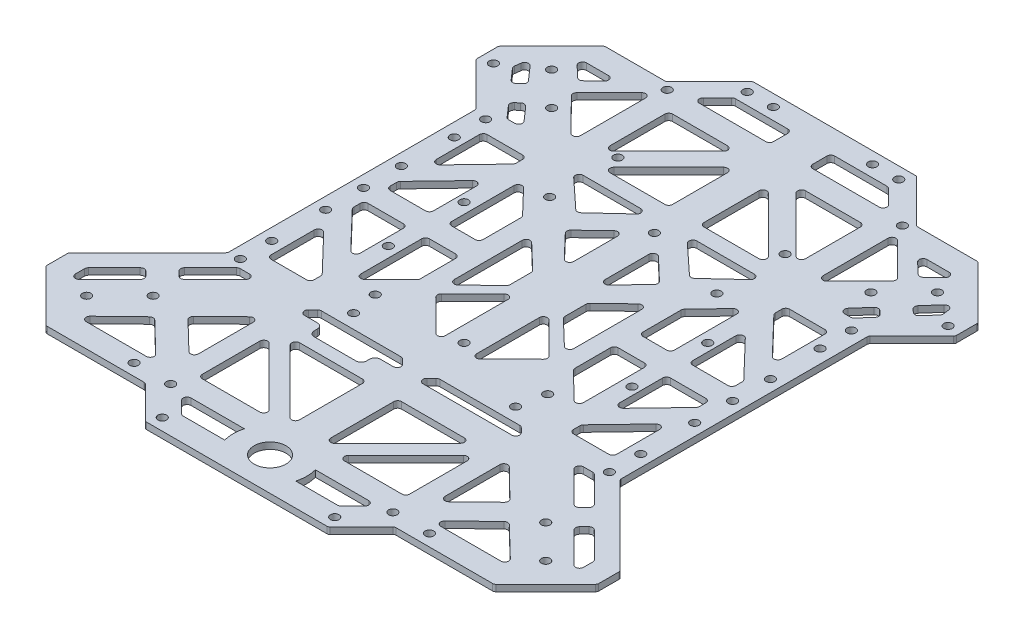
SolidWorks part; units mm, degrees
other "Kamera1"
ref_plane "Ön Düzlem" through (0, 0, 0) normal (0, 0, 1) x (1, 0, 0)
ref_plane "Üst Düzlem" through (0, 0, 0) normal (0, 1, 0) x (1, 0, 0)
ref_plane "Sağ Düzlem" through (0, 0, 0) normal (1, 0, 0) x (0, 0, -1)
sketch "Çizim1" plane through (0, 0, 0) normal (0, 1, 0) x (1, 0, 0)
  line L0 (-126.5115, 0) -> (-22.8808, 0) construction
  line L1 (0, -165.8604) -> (0, 125.495) construction
  line L10 (105.5269, -77.9056) -> (75.1213, -47.5)
  line L11 (105.5269, -86.6056) -> (105.5269, -77.9056)
  line L12 (85.7279, -106.4046) -> (105.5269, -86.6056)
  line L13 (47.7279, -106.4046) -> (85.7279, -106.4046)
  line L14 (35, -119.1325) -> (47.7279, -106.4046)
  line L15 (35, -119.1325) -> (-35, -119.1325)
  line L17 (75.1213, -47.5) -> (75.1213, 0)
  line L19 (6, -104.1325) -> (6, -108.6325)
  line L20 (7.5, -110.1325) -> (29.5, -110.1325)
  line L21 (30.5607, -109.6932) -> (35.0607, -105.1932)
  line L22 (34, -102.6325) -> (7.5, -102.6325)
  line L24 (39.6933, -70.6325) -> (39.6933, -92.6325)
  line L25 (38.1933, -94.1325) -> (16.1933, -94.1325)
  line L26 (15.1326, -91.5718) -> (37.1326, -69.5718)
  line L27 (6, -65.0493) -> (6, -89.1325)
  line L28 (8.5625, -90.1913) -> (32.5625, -66.1081)
  line L29 (31.5, -63.5493) -> (7.5, -63.5493)
  line L30 (66.8113, -83.7022) -> (55.3113, -94.8265)
  line L31 (56.3542, -97.4046) -> (79.3542, -97.4046)
  line L32 (80.3971, -94.8265) -> (68.8971, -83.7022)
  line L36 (49.7362, -87.6977) -> (60.5174, -77.2687)
  line L37 (60.5247, -75.1195) -> (49.7434, -64.5485)
  line L38 (47.1933, -65.6196) -> (47.1933, -86.6196)
  line L39 (21.6344, -34.0457) -> (4.6344, -50.9868)
  line L40 (5.6933, -53.5493) -> (39.6933, -53.5493)
  line L41 (40.7521, -50.9868) -> (23.7521, -34.0457)
  line L42 (6, -9.3078) -> (6, -33.3078)
  line L43 (8.5588, -34.3703) -> (20.6004, -22.3703)
  line L44 (20.6004, -20.2453) -> (8.5588, -8.2453)
  line L45 (10.5, 4) -> (10.5, -4)
  line L46 (10.9615, -5.0824) -> (20.3424, -14.0824)
  line L47 (22.8808, -13) -> (22.8808, 13)
  line L49 (84.7746, -69.1741) -> (83.0069, -70.9419)
  line L50 (83.0069, -73.0632) -> (94.6741, -84.7305)
  line L51 (97.2348, -83.6698) -> (97.2348, -80.1343)
  line L52 (96.7954, -79.0736) -> (86.8959, -69.1741)
  line L53 (87.603, -59.9817) -> (82.3234, -65.2614) construction
  line L54 (63.915, -50.35) -> (67.4505, -50.35)
  line L55 (74.5216, -64.5779) -> (62.8543, -52.9107)
  line L56 (78.4107, -62.8102) -> (76.6429, -64.5779)
  line L57 (68.5112, -50.7893) -> (78.4107, -60.6888)
  line L58 (51.1213, -41.35) -> (64.6213, -41.35)
  line L59 (66.1213, -39.85) -> (66.1213, -23.35)
  line L60 (63.5389, -22.3115) -> (50.0389, -36.3828)
  line L61 (49.6213, -37.4212) -> (49.6213, -39.85)
  line L62 (49.6213, -5.7546) -> (49.6213, -22.2546)
  line L63 (52.2037, -23.293) -> (65.7037, -9.2218)
  line L64 (66.1213, -8.1833) -> (66.1213, -5.7546)
  line L65 (64.6213, -4.2546) -> (51.1213, -4.2546)
  line L66 (29.6213, -5.75) -> (29.6213, -19.25)
  line L67 (30.0715, -20.3214) -> (40.0715, -30.1194)
  line L68 (42.6213, -29.048) -> (42.6213, -5.75)
  line L69 (41.1213, -4.25) -> (31.1213, -4.25)
  line L70 (-105.5269, -86.6056) -> (-105.5269, -77.9056)
  line L71 (-105.5269, -77.9056) -> (-75.1213, -47.5)
  line L72 (-85.7279, -106.4046) -> (-105.5269, -86.6056)
  line L73 (-87.603, -59.9817) -> (-82.3234, -65.2614) construction
  line L74 (-41.1213, -4.25) -> (-31.1213, -4.25)
  line L75 (-42.6213, -29.048) -> (-42.6213, -5.75)
  line L76 (-30.0715, -20.3214) -> (-40.0715, -30.1194)
  line L77 (-29.6213, -5.75) -> (-29.6213, -19.25)
  line L78 (-64.6213, -4.2546) -> (-51.1213, -4.2546)
  line L79 (-66.1213, -8.1833) -> (-66.1213, -5.7546)
  line L80 (-52.2037, -23.293) -> (-65.7037, -9.2218)
  line L81 (-49.6213, -5.7546) -> (-49.6213, -22.2546)
  line L82 (-49.6213, -37.4212) -> (-49.6213, -39.85)
  line L83 (-63.5389, -22.3115) -> (-50.0389, -36.3828)
  line L84 (-66.1213, -39.85) -> (-66.1213, -23.35)
  line L85 (-51.1213, -41.35) -> (-64.6213, -41.35)
  line L86 (-68.5112, -50.7893) -> (-78.4107, -60.6888)
  line L87 (-78.4107, -62.8102) -> (-76.6429, -64.5779)
  line L88 (-74.5216, -64.5779) -> (-62.8543, -52.9107)
  line L89 (-63.915, -50.35) -> (-67.4505, -50.35)
  line L90 (-96.7954, -79.0736) -> (-86.8959, -69.1741)
  line L91 (-97.2348, -83.6698) -> (-97.2348, -80.1343)
  line L92 (-83.0069, -73.0632) -> (-94.6741, -84.7305)
  line L93 (-84.7746, -69.1741) -> (-83.0069, -70.9419)
  line L95 (-22.8808, -13) -> (-22.8808, 0)
  line L96 (-10.9615, -5.0824) -> (-20.3424, -14.0824)
  line L97 (-10.5, 0) -> (-10.5, -4)
  line L98 (-20.6004, -20.2453) -> (-8.5588, -8.2453)
  line L99 (-8.5588, -34.3703) -> (-20.6004, -22.3703)
  line L100 (-6, -9.3078) -> (-6, -33.3078)
  line L101 (-40.7521, -50.9868) -> (-23.7521, -34.0457)
  line L102 (-5.6933, -53.5493) -> (-39.6933, -53.5493)
  line L103 (-21.6344, -34.0457) -> (-4.6344, -50.9868)
  line L104 (-47.1933, -65.6196) -> (-47.1933, -86.6196)
  line L105 (-60.5247, -75.1195) -> (-49.7434, -64.5485)
  line L106 (-49.7362, -87.6977) -> (-60.5174, -77.2687)
  line L107 (-80.3971, -94.8265) -> (-68.8971, -83.7022)
  line L108 (-56.3542, -97.4046) -> (-79.3542, -97.4046)
  line L109 (-66.8113, -83.7022) -> (-55.3113, -94.8265)
  line L110 (-31.5, -63.5493) -> (-7.5, -63.5493)
  line L111 (-8.5625, -90.1913) -> (-32.5625, -66.1081)
  line L112 (-6, -65.0493) -> (-6, -89.1325)
  line L113 (-15.1326, -91.5718) -> (-37.1326, -69.5718)
  line L114 (-38.1933, -94.1325) -> (-16.1933, -94.1325)
  line L115 (-39.6933, -70.6325) -> (-39.6933, -92.6325)
  line L116 (-34, -102.6325) -> (-7.5, -102.6325)
  line L117 (-30.5607, -109.6932) -> (-35.0607, -105.1932)
  line L118 (-7.5, -110.1325) -> (-29.5, -110.1325)
  line L119 (-6, -104.1325) -> (-6, -108.6325)
  line L120 (-75.1213, -47.5) -> (-75.1213, 0)
  line L121 (-35, -119.1325) -> (-47.7279, -106.4046)
  line L122 (-47.7279, -106.4046) -> (-85.7279, -106.4046)
  line L124 (75.1213, 0) -> (75.1213, 47.5)
  line L125 (75.1213, 47.5) -> (91.7383, 64.117)
  line L126 (91.7383, 64.117) -> (91.7383, 72.817)
  line L127 (91.7383, 72.817) -> (71.4444, 93.111)
  line L128 (71.4444, 93.111) -> (47.9444, 93.111)
  line L129 (47.9444, 93.111) -> (31.3274, 109.728)
  line L130 (31.3274, 109.728) -> (-31.3274, 109.728)
  line L131 (63.5389, 22.3115) -> (50.0389, 36.3828)
  line L132 (66.1213, 39.85) -> (66.1213, 23.35)
  line L133 (51.1213, 41.35) -> (64.6213, 41.35)
  line L134 (49.6213, 37.4212) -> (49.6213, 39.85)
  line L135 (66.1213, 8.1833) -> (66.1213, 5.7546)
  line L136 (52.2037, 23.293) -> (65.7037, 9.2218)
  line L137 (49.6213, 5.7546) -> (49.6213, 22.2546)
  line L138 (64.6213, 4.2546) -> (51.1213, 4.2546)
  line L139 (41.1213, 4.2546) -> (32.1213, 4.2546)
  line L140 (30.6213, 5.7546) -> (30.6213, 20.2546)
  line L141 (31.0389, 21.293) -> (40.0389, 30.6739)
  line L142 (42.6213, 29.6354) -> (42.6213, 5.7546)
  line L143 (10.9615, 5.0824) -> (20.3424, 14.0824)
  line L144 (22.8808, 0) -> (141.8188, 0) construction
  line L145 (62.0023, 52.8424) -> (66.6337, 58.0913)
  line L146 (68.7509, 58.2236) -> (70.0256, 57.0989)
  line L147 (70.1579, 54.9817) -> (66.519, 50.8576)
  line L150 (65.3942, 50.35) -> (63.1271, 50.35)
  line L151 (70.1198, 63.017) -> (74.1298, 59.4788) construction
  line L152 (78.0974, 63.9797) -> (81.7363, 68.1038)
  line L153 (74.7055, 64.9722) -> (75.9802, 63.8474)
  line L154 (79.2045, 72.3382) -> (74.5731, 67.0894)
  line L155 (82.0999, 69.283) -> (81.8176, 71.5326)
  line L156 (60.9579, 84.111) -> (69.3579, 84.111)
  line L157 (70.3923, 81.5248) -> (66.1923, 77.5248)
  line L158 (64.1234, 77.5248) -> (59.9234, 81.5248)
  line L159 (6, 32.6354) -> (6, 15.8354)
  line L160 (8.585, 14.7997) -> (16.976, 23.5902)
  line L161 (16.9266, 25.7109) -> (8.5357, 33.7204)
  line L162 (9.7302, 43.598) -> (20.7302, 33.4)
  line L163 (22.7698, 33.4) -> (33.7698, 43.598)
  line L164 (32.75, 46.198) -> (10.75, 46.198)
  line L165 (9, 100.728) -> (29.0094, 100.728)
  line L166 (30.071, 100.2877) -> (35.4616, 94.8877)
  line L167 (34.4, 92.328) -> (9, 92.328)
  line L168 (7.5, 93.828) -> (7.5, 99.228)
  line L169 (6, 74.698) -> (6, 53.698)
  line L170 (7.5, 52.198) -> (28.5, 52.198)
  line L171 (29.5607, 54.7587) -> (8.5607, 75.7587)
  line L172 (16.4335, 73.1892) -> (24.0883, 65.5343) construction
  line L173 (37.4246, 82.1227) -> (37.4246, 61.1227)
  line L174 (14.9246, 83.6227) -> (35.9246, 83.6227)
  line L175 (34.864, 60.062) -> (13.864, 81.062)
  line L176 (46.4246, 83.7244) -> (46.4246, 58.8244)
  line L177 (48.9917, 57.7702) -> (61.3661, 70.2958)
  line L178 (61.3597, 72.4107) -> (48.9853, 84.785)
  line L179 (-10.5, 0) -> (10.5, 0) construction
  line L180 (-22.8808, -13) -> (-22.8808, 13)
  line L181 (-10.5, 4) -> (-10.5, -4)
  line L182 (-75.1213, 0) -> (-75.1213, 47.5)
  line L183 (-16.4335, 73.1892) -> (-24.0883, 65.5343) construction
  line L184 (-61.3597, 72.4107) -> (-48.9853, 84.785)
  line L185 (-48.9917, 57.7702) -> (-61.3661, 70.2958)
  line L186 (-46.4246, 83.7244) -> (-46.4246, 58.8244)
  line L187 (-34.864, 60.062) -> (-13.864, 81.062)
  line L188 (-14.9246, 83.6227) -> (-35.9246, 83.6227)
  line L189 (-37.4246, 82.1227) -> (-37.4246, 61.1227)
  line L190 (-29.5607, 54.7587) -> (-8.5607, 75.7587)
  line L191 (-7.5, 52.198) -> (-28.5, 52.198)
  line L192 (-6, 74.698) -> (-6, 53.698)
  line L193 (-7.5, 93.828) -> (-7.5, 99.228)
  line L194 (-34.4, 92.328) -> (-9, 92.328)
  line L195 (-30.071, 100.2877) -> (-35.4616, 94.8877)
  line L196 (-9, 100.728) -> (-29.0094, 100.728)
  line L197 (-32.75, 46.198) -> (-10.75, 46.198)
  line L198 (-22.7698, 33.4) -> (-33.7698, 43.598)
  line L199 (-9.7302, 43.598) -> (-20.7302, 33.4)
  line L200 (-16.9266, 25.7109) -> (-8.5357, 33.7204)
  line L201 (-8.585, 14.7997) -> (-16.976, 23.5902)
  line L202 (-6, 32.6354) -> (-6, 15.8354)
  line L203 (-64.1234, 77.5248) -> (-59.9234, 81.5248)
  line L204 (-70.3923, 81.5248) -> (-66.1923, 77.5248)
  line L205 (-60.9579, 84.111) -> (-69.3579, 84.111)
  line L206 (-82.0999, 69.283) -> (-81.8176, 71.5326)
  line L207 (-79.2045, 72.3382) -> (-74.5731, 67.0894)
  line L208 (-74.7055, 64.9722) -> (-75.9802, 63.8474)
  line L209 (-78.0974, 63.9797) -> (-81.7363, 68.1038)
  line L210 (-10.9615, 5.0824) -> (-20.3424, 14.0824)
  line L211 (-42.6213, 29.6354) -> (-42.6213, 5.7546)
  line L212 (-31.0389, 21.293) -> (-40.0389, 30.6739)
  line L213 (-30.6213, 5.7546) -> (-30.6213, 20.2546)
  line L214 (-41.1213, 4.2546) -> (-32.1213, 4.2546)
  line L215 (-64.6213, 4.2546) -> (-51.1213, 4.2546)
  line L216 (-49.6213, 5.7546) -> (-49.6213, 22.2546)
  line L217 (-52.2037, 23.293) -> (-65.7037, 9.2218)
  line L218 (-66.1213, 8.1833) -> (-66.1213, 5.7546)
  line L219 (-49.6213, 37.4212) -> (-49.6213, 39.85)
  line L220 (-51.1213, 41.35) -> (-64.6213, 41.35)
  line L221 (-66.1213, 39.85) -> (-66.1213, 23.35)
  line L222 (-63.5389, 22.3115) -> (-50.0389, 36.3828)
  line L223 (-47.9444, 93.111) -> (-31.3274, 109.728)
  line L224 (-71.4444, 93.111) -> (-47.9444, 93.111)
  line L225 (-91.7383, 72.817) -> (-71.4444, 93.111)
  line L226 (-91.7383, 64.117) -> (-91.7383, 72.817)
  line L227 (-75.1213, 47.5) -> (-91.7383, 64.117)
  line L228 (-70.1579, 54.9817) -> (-66.519, 50.8576)
  line L229 (-68.7509, 58.2236) -> (-70.0256, 57.0989)
  line L230 (-62.0023, 52.8424) -> (-66.6337, 58.0913)
  line L231 (-65.3942, 50.35) -> (-63.1271, 50.35)
  arc A0 (29.5, -110.1325) -> (30.5607, -109.6932) centre (29.5, -108.6325) ccw
  arc A1 (35.0607, -105.1932) -> (34, -102.6325) centre (34, -104.1325) ccw
  arc A2 (6, -104.1325) -> (7.5, -102.6325) centre (7.5, -104.1325) cw
  arc A3 (6, -108.6325) -> (7.5, -110.1325) centre (7.5, -108.6325) ccw
  arc A4 (39.6933, -70.6325) -> (37.1326, -69.5718) centre (38.1933, -70.6325) ccw
  arc A5 (39.6933, -92.6325) -> (38.1933, -94.1325) centre (38.1933, -92.6325) cw
  arc A6 (16.1933, -94.1325) -> (15.1326, -91.5718) centre (16.1933, -92.6325) cw
  arc A7 (6, -89.1325) -> (8.5625, -90.1913) centre (7.5, -89.1325) ccw
  arc A8 (32.5625, -66.1081) -> (31.5, -63.5493) centre (31.5, -65.0493) ccw
  arc A9 (6, -65.0493) -> (7.5, -63.5493) centre (7.5, -65.0493) cw
  arc A10 (79.3542, -97.4046) -> (80.3971, -94.8265) centre (79.3542, -95.9046) ccw
  arc A11 (55.3113, -94.8265) -> (56.3542, -97.4046) centre (56.3542, -95.9046) ccw
  arc A12 (66.8113, -83.7022) -> (68.8971, -83.7022) centre (67.8542, -84.7803) cw
  arc A16 (60.5174, -77.2687) -> (60.5247, -75.1195) centre (59.4745, -76.1905) ccw
  arc A17 (49.7434, -64.5485) -> (47.1933, -65.6196) centre (48.6933, -65.6196) ccw
  arc A18 (49.7362, -87.6977) -> (47.1933, -86.6196) centre (48.6933, -86.6196) cw
  arc A19 (39.6933, -53.5493) -> (40.7521, -50.9868) centre (39.6933, -52.0493) ccw
  arc A20 (4.6344, -50.9868) -> (5.6933, -53.5493) centre (5.6933, -52.0493) ccw
  arc A21 (21.6344, -34.0457) -> (23.7521, -34.0457) centre (22.6933, -35.1082) cw
  arc A22 (6, -9.3078) -> (8.5588, -8.2453) centre (7.5, -9.3078) cw
  arc A23 (20.6004, -22.3703) -> (20.6004, -20.2453) centre (19.5416, -21.3078) ccw
  arc A24 (6, -33.3078) -> (8.5588, -34.3703) centre (7.5, -33.3078) ccw
  arc A25 (20.3424, -14.0824) -> (22.8808, -13) centre (21.3808, -13) ccw
  arc A26 (10.5, -4) -> (10.9615, -5.0824) centre (12, -4) ccw
  arc A27 (83.0069, -70.9419) -> (83.0069, -73.0632) centre (84.0675, -72.0025) ccw
  arc A28 (84.7746, -69.1741) -> (86.8959, -69.1741) centre (85.8353, -70.2348) cw
  arc A29 (97.2348, -80.1343) -> (96.7954, -79.0736) centre (95.7348, -80.1343) ccw
  arc A30 (94.6741, -84.7305) -> (97.2348, -83.6698) centre (95.7348, -83.6698) ccw
  arc A31 (62.8543, -52.9107) -> (63.915, -50.35) centre (63.915, -51.85) cw
  arc A32 (76.6429, -64.5779) -> (74.5216, -64.5779) centre (75.5822, -63.5173) cw
  arc A33 (78.4107, -62.8102) -> (78.4107, -60.6888) centre (77.35, -61.7495) ccw
  arc A34 (67.4505, -50.35) -> (68.5112, -50.7893) centre (67.4505, -51.85) cw
  arc A35 (66.1213, -23.35) -> (63.5389, -22.3115) centre (64.6213, -23.35) ccw
  arc A36 (64.6213, -41.35) -> (66.1213, -39.85) centre (64.6213, -39.85) ccw
  arc A37 (51.1213, -41.35) -> (49.6213, -39.85) centre (51.1213, -39.85) cw
  arc A38 (50.0389, -36.3828) -> (49.6213, -37.4212) centre (51.1213, -37.4212) ccw
  arc A39 (66.1213, -5.7546) -> (64.6213, -4.2546) centre (64.6213, -5.7546) ccw
  arc A40 (65.7037, -9.2218) -> (66.1213, -8.1833) centre (64.6213, -8.1833) ccw
  arc A41 (49.6213, -22.2546) -> (52.2037, -23.293) centre (51.1213, -22.2546) ccw
  arc A42 (49.6213, -5.7546) -> (51.1213, -4.2546) centre (51.1213, -5.7546) cw
  arc A43 (29.6213, -5.75) -> (31.1213, -4.25) centre (31.1213, -5.75) cw
  arc A44 (42.6213, -5.75) -> (41.1213, -4.25) centre (41.1213, -5.75) ccw
  arc A45 (40.0715, -30.1194) -> (42.6213, -29.048) centre (41.1213, -29.048) ccw
  arc A46 (29.6213, -19.25) -> (30.0715, -20.3214) centre (31.1213, -19.25) ccw
  arc A47 (-29.6213, -19.25) -> (-30.0715, -20.3214) centre (-31.1213, -19.25) cw
  arc A48 (-40.0715, -30.1194) -> (-42.6213, -29.048) centre (-41.1213, -29.048) cw
  arc A49 (-42.6213, -5.75) -> (-41.1213, -4.25) centre (-41.1213, -5.75) cw
  arc A50 (-29.6213, -5.75) -> (-31.1213, -4.25) centre (-31.1213, -5.75) ccw
  arc A51 (-49.6213, -5.7546) -> (-51.1213, -4.2546) centre (-51.1213, -5.7546) ccw
  arc A52 (-49.6213, -22.2546) -> (-52.2037, -23.293) centre (-51.1213, -22.2546) cw
  arc A53 (-65.7037, -9.2218) -> (-66.1213, -8.1833) centre (-64.6213, -8.1833) cw
  arc A54 (-66.1213, -5.7546) -> (-64.6213, -4.2546) centre (-64.6213, -5.7546) cw
  arc A55 (-50.0389, -36.3828) -> (-49.6213, -37.4212) centre (-51.1213, -37.4212) cw
  arc A56 (-51.1213, -41.35) -> (-49.6213, -39.85) centre (-51.1213, -39.85) ccw
  arc A57 (-64.6213, -41.35) -> (-66.1213, -39.85) centre (-64.6213, -39.85) cw
  arc A58 (-66.1213, -23.35) -> (-63.5389, -22.3115) centre (-64.6213, -23.35) cw
  arc A59 (-67.4505, -50.35) -> (-68.5112, -50.7893) centre (-67.4505, -51.85) ccw
  arc A60 (-78.4107, -62.8102) -> (-78.4107, -60.6888) centre (-77.35, -61.7495) cw
  arc A61 (-76.6429, -64.5779) -> (-74.5216, -64.5779) centre (-75.5822, -63.5173) ccw
  arc A62 (-62.8543, -52.9107) -> (-63.915, -50.35) centre (-63.915, -51.85) ccw
  arc A63 (-94.6741, -84.7305) -> (-97.2348, -83.6698) centre (-95.7348, -83.6698) cw
  arc A64 (-97.2348, -80.1343) -> (-96.7954, -79.0736) centre (-95.7348, -80.1343) cw
  arc A65 (-84.7746, -69.1741) -> (-86.8959, -69.1741) centre (-85.8353, -70.2348) ccw
  arc A66 (-83.0069, -70.9419) -> (-83.0069, -73.0632) centre (-84.0675, -72.0025) cw
  arc A67 (-10.5, -4) -> (-10.9615, -5.0824) centre (-12, -4) cw
  arc A68 (-20.3424, -14.0824) -> (-22.8808, -13) centre (-21.3808, -13) cw
  arc A69 (-6, -33.3078) -> (-8.5588, -34.3703) centre (-7.5, -33.3078) cw
  arc A70 (-20.6004, -22.3703) -> (-20.6004, -20.2453) centre (-19.5416, -21.3078) cw
  arc A71 (-6, -9.3078) -> (-8.5588, -8.2453) centre (-7.5, -9.3078) ccw
  arc A72 (-21.6344, -34.0457) -> (-23.7521, -34.0457) centre (-22.6933, -35.1082) ccw
  arc A73 (-4.6344, -50.9868) -> (-5.6933, -53.5493) centre (-5.6933, -52.0493) cw
  arc A74 (-39.6933, -53.5493) -> (-40.7521, -50.9868) centre (-39.6933, -52.0493) cw
  arc A75 (-49.7362, -87.6977) -> (-47.1933, -86.6196) centre (-48.6933, -86.6196) ccw
  arc A76 (-49.7434, -64.5485) -> (-47.1933, -65.6196) centre (-48.6933, -65.6196) cw
  arc A77 (-60.5174, -77.2687) -> (-60.5247, -75.1195) centre (-59.4745, -76.1905) cw
  arc A78 (-66.8113, -83.7022) -> (-68.8971, -83.7022) centre (-67.8542, -84.7803) ccw
  arc A79 (-55.3113, -94.8265) -> (-56.3542, -97.4046) centre (-56.3542, -95.9046) cw
  arc A80 (-79.3542, -97.4046) -> (-80.3971, -94.8265) centre (-79.3542, -95.9046) cw
  arc A81 (-6, -65.0493) -> (-7.5, -63.5493) centre (-7.5, -65.0493) ccw
  arc A82 (-32.5625, -66.1081) -> (-31.5, -63.5493) centre (-31.5, -65.0493) cw
  arc A83 (-6, -89.1325) -> (-8.5625, -90.1913) centre (-7.5, -89.1325) cw
  arc A84 (-16.1933, -94.1325) -> (-15.1326, -91.5718) centre (-16.1933, -92.6325) ccw
  arc A85 (-39.6933, -92.6325) -> (-38.1933, -94.1325) centre (-38.1933, -92.6325) ccw
  arc A86 (-39.6933, -70.6325) -> (-37.1326, -69.5718) centre (-38.1933, -70.6325) cw
  arc A87 (-6, -108.6325) -> (-7.5, -110.1325) centre (-7.5, -108.6325) cw
  arc A88 (-6, -104.1325) -> (-7.5, -102.6325) centre (-7.5, -104.1325) ccw
  arc A89 (-35.0607, -105.1932) -> (-34, -102.6325) centre (-34, -104.1325) cw
  arc A90 (-29.5, -110.1325) -> (-30.5607, -109.6932) centre (-29.5, -108.6325) cw
  arc A91 (66.1213, 23.35) -> (63.5389, 22.3115) centre (64.6213, 23.35) cw
  arc A92 (64.6213, 41.35) -> (66.1213, 39.85) centre (64.6213, 39.85) cw
  arc A93 (51.1213, 41.35) -> (49.6213, 39.85) centre (51.1213, 39.85) ccw
  arc A94 (50.0389, 36.3828) -> (49.6213, 37.4212) centre (51.1213, 37.4212) cw
  arc A95 (65.7037, 9.2218) -> (66.1213, 8.1833) centre (64.6213, 8.1833) cw
  arc A96 (49.6213, 22.2546) -> (52.2037, 23.293) centre (51.1213, 22.2546) cw
  arc A97 (66.1213, 5.7546) -> (64.6213, 4.2546) centre (64.6213, 5.7546) cw
  arc A98 (49.6213, 5.7546) -> (51.1213, 4.2546) centre (51.1213, 5.7546) ccw
  arc A99 (32.1213, 4.2546) -> (30.6213, 5.7546) centre (32.1213, 5.7546) cw
  arc A100 (41.1213, 4.2546) -> (42.6213, 5.7546) centre (41.1213, 5.7546) ccw
  arc A101 (40.0389, 30.6739) -> (42.6213, 29.6354) centre (41.1213, 29.6354) cw
  arc A102 (30.6213, 20.2546) -> (31.0389, 21.293) centre (32.1213, 20.2546) cw
  arc A103 (10.5, 4) -> (10.9615, 5.0824) centre (12, 4) cw
  arc A104 (20.3424, 14.0824) -> (22.8808, 13) centre (21.3808, 13) cw
  arc A105 (66.6337, 58.0913) -> (68.7509, 58.2236) centre (67.7584, 57.0989) cw
  arc A106 (70.0256, 57.0989) -> (70.1579, 54.9817) centre (69.0332, 55.9741) cw
  arc A107 (66.519, 50.8576) -> (65.3942, 50.35) centre (65.3942, 51.85) cw
  arc A108 (62.0023, 52.8424) -> (63.1271, 50.35) centre (63.1271, 51.85) ccw
  arc A109 (75.9802, 63.8474) -> (78.0974, 63.9797) centre (76.9726, 64.9722) ccw
  arc A110 (74.5731, 67.0894) -> (74.7055, 64.9722) centre (75.6979, 66.0969) ccw
  arc A111 (81.7363, 68.1038) -> (82.0999, 69.283) centre (80.6115, 69.0963) ccw
  arc A112 (79.2045, 72.3382) -> (81.8176, 71.5326) centre (80.3292, 71.3458) cw
  arc A113 (69.3579, 84.111) -> (70.3923, 81.5248) centre (69.3579, 82.611) cw
  arc A114 (66.1923, 77.5248) -> (64.1234, 77.5248) centre (65.1579, 78.611) cw
  arc A115 (60.9579, 84.111) -> (59.9234, 81.5248) centre (60.9579, 82.611) ccw
  arc A116 (16.976, 23.5902) -> (16.9266, 25.7109) centre (15.8909, 24.6259) ccw
  arc A117 (6, 15.8354) -> (8.585, 14.7997) centre (7.5, 15.8354) ccw
  arc A118 (6, 32.6354) -> (8.5357, 33.7204) centre (7.5, 32.6354) cw
  arc A119 (33.7698, 43.598) -> (32.75, 46.198) centre (32.75, 44.698) ccw
  arc A120 (20.7302, 33.4) -> (22.7698, 33.4) centre (21.75, 34.5) ccw
  arc A121 (9.7302, 43.598) -> (10.75, 46.198) centre (10.75, 44.698) cw
  arc A122 (35.4616, 94.8877) -> (34.4, 92.328) centre (34.4, 93.828) cw
  arc A123 (29.0094, 100.728) -> (30.071, 100.2877) centre (29.0094, 99.228) cw
  arc A124 (9, 100.728) -> (7.5, 99.228) centre (9, 99.228) ccw
  arc A125 (9, 92.328) -> (7.5, 93.828) centre (9, 93.828) cw
  arc A126 (28.5, 52.198) -> (29.5607, 54.7587) centre (28.5, 53.698) ccw
  arc A127 (6, 53.698) -> (7.5, 52.198) centre (7.5, 53.698) ccw
  arc A128 (6, 74.698) -> (8.5607, 75.7587) centre (7.5, 74.698) cw
  arc A129 (35.9246, 83.6227) -> (37.4246, 82.1227) centre (35.9246, 82.1227) cw
  arc A130 (37.4246, 61.1227) -> (34.864, 60.062) centre (35.9246, 61.1227) cw
  arc A131 (14.9246, 83.6227) -> (13.864, 81.062) centre (14.9246, 82.1227) ccw
  arc A132 (46.4246, 83.7244) -> (48.9853, 84.785) centre (47.9246, 83.7244) cw
  arc A133 (46.4246, 58.8244) -> (48.9917, 57.7702) centre (47.9246, 58.8244) ccw
  arc A134 (61.3661, 70.2958) -> (61.3597, 72.4107) centre (60.299, 71.35) ccw
  arc A135 (-61.3661, 70.2958) -> (-61.3597, 72.4107) centre (-60.299, 71.35) cw
  arc A136 (-46.4246, 58.8244) -> (-48.9917, 57.7702) centre (-47.9246, 58.8244) cw
  arc A137 (-46.4246, 83.7244) -> (-48.9853, 84.785) centre (-47.9246, 83.7244) ccw
  arc A138 (-14.9246, 83.6227) -> (-13.864, 81.062) centre (-14.9246, 82.1227) cw
  arc A139 (-37.4246, 61.1227) -> (-34.864, 60.062) centre (-35.9246, 61.1227) ccw
  arc A140 (-35.9246, 83.6227) -> (-37.4246, 82.1227) centre (-35.9246, 82.1227) ccw
  arc A141 (-6, 74.698) -> (-8.5607, 75.7587) centre (-7.5, 74.698) ccw
  arc A142 (-6, 53.698) -> (-7.5, 52.198) centre (-7.5, 53.698) cw
  arc A143 (-28.5, 52.198) -> (-29.5607, 54.7587) centre (-28.5, 53.698) cw
  arc A144 (-9, 92.328) -> (-7.5, 93.828) centre (-9, 93.828) ccw
  arc A145 (-9, 100.728) -> (-7.5, 99.228) centre (-9, 99.228) cw
  arc A146 (-29.0094, 100.728) -> (-30.071, 100.2877) centre (-29.0094, 99.228) ccw
  arc A147 (-35.4616, 94.8877) -> (-34.4, 92.328) centre (-34.4, 93.828) ccw
  arc A148 (-9.7302, 43.598) -> (-10.75, 46.198) centre (-10.75, 44.698) ccw
  arc A149 (-20.7302, 33.4) -> (-22.7698, 33.4) centre (-21.75, 34.5) cw
  arc A150 (-33.7698, 43.598) -> (-32.75, 46.198) centre (-32.75, 44.698) cw
  arc A151 (-6, 32.6354) -> (-8.5357, 33.7204) centre (-7.5, 32.6354) ccw
  arc A152 (-6, 15.8354) -> (-8.585, 14.7997) centre (-7.5, 15.8354) cw
  arc A153 (-16.976, 23.5902) -> (-16.9266, 25.7109) centre (-15.8909, 24.6259) cw
  arc A154 (-60.9579, 84.111) -> (-59.9234, 81.5248) centre (-60.9579, 82.611) cw
  arc A155 (-66.1923, 77.5248) -> (-64.1234, 77.5248) centre (-65.1579, 78.611) ccw
  arc A156 (-69.3579, 84.111) -> (-70.3923, 81.5248) centre (-69.3579, 82.611) ccw
  arc A157 (-79.2045, 72.3382) -> (-81.8176, 71.5326) centre (-80.3292, 71.3458) ccw
  arc A158 (-81.7363, 68.1038) -> (-82.0999, 69.283) centre (-80.6115, 69.0963) cw
  arc A159 (-74.5731, 67.0894) -> (-74.7055, 64.9722) centre (-75.6979, 66.0969) cw
  arc A160 (-75.9802, 63.8474) -> (-78.0974, 63.9797) centre (-76.9726, 64.9722) cw
  arc A161 (-20.3424, 14.0824) -> (-22.8808, 13) centre (-21.3808, 13) ccw
  arc A162 (-10.5, 4) -> (-10.9615, 5.0824) centre (-12, 4) ccw
  arc A163 (-30.6213, 20.2546) -> (-31.0389, 21.293) centre (-32.1213, 20.2546) ccw
  arc A164 (-40.0389, 30.6739) -> (-42.6213, 29.6354) centre (-41.1213, 29.6354) ccw
  arc A165 (-41.1213, 4.2546) -> (-42.6213, 5.7546) centre (-41.1213, 5.7546) cw
  arc A166 (-32.1213, 4.2546) -> (-30.6213, 5.7546) centre (-32.1213, 5.7546) ccw
  arc A167 (-49.6213, 5.7546) -> (-51.1213, 4.2546) centre (-51.1213, 5.7546) cw
  arc A168 (-66.1213, 5.7546) -> (-64.6213, 4.2546) centre (-64.6213, 5.7546) ccw
  arc A169 (-49.6213, 22.2546) -> (-52.2037, 23.293) centre (-51.1213, 22.2546) ccw
  arc A170 (-65.7037, 9.2218) -> (-66.1213, 8.1833) centre (-64.6213, 8.1833) ccw
  arc A171 (-50.0389, 36.3828) -> (-49.6213, 37.4212) centre (-51.1213, 37.4212) ccw
  arc A172 (-51.1213, 41.35) -> (-49.6213, 39.85) centre (-51.1213, 39.85) cw
  arc A173 (-64.6213, 41.35) -> (-66.1213, 39.85) centre (-64.6213, 39.85) ccw
  arc A174 (-66.1213, 23.35) -> (-63.5389, 22.3115) centre (-64.6213, 23.35) ccw
  arc A175 (-70.0256, 57.0989) -> (-70.1579, 54.9817) centre (-69.0332, 55.9741) ccw
  arc A176 (-66.6337, 58.0913) -> (-68.7509, 58.2236) centre (-67.7584, 57.0989) ccw
  arc A177 (-66.519, 50.8576) -> (-65.3942, 50.35) centre (-65.3942, 51.85) ccw
  arc A178 (-62.0023, 52.8424) -> (-63.1271, 50.35) centre (-63.1271, 51.85) cw
  point P14 (75.1213, 0)
  point P24 (0, -119.1325)
  point P29 (-95, 0)
  point P33 (0, 119.1325)
  point P105 (83.8907, -70.058)
  point P152 (42.6213, -32.6177)
  point P155 (29.6213, -19.8803)
  point P298 (0, -119.1325)
  point P299 (-29.6213, -19.8803)
  point P300 (-42.6213, -32.6177)
  point P301 (-75.1213, 0)
  point P357 (67.6261, 59.2161)
  point P360 (71.1503, 56.1064)
  point P363 (66.0711, 50.35)
  point P366 (59.8031, 50.35)
  point P367 (69.3882, 57.6612)
  point P368 (64.2607, 50.35)
  point P577 (0, 109.728)
  dimension "D18" = 1.5
  dimension "D15" = 28
  dimension "D19" = 1.5
  dimension "D24" = 1.5
  dimension "D29" = 1.5
  dimension "D35" = 1.5
  dimension "D39" = 1.5
  dimension "D28" = 1.5
  dimension "D51" = 1.5
  dimension "D55" = 1.5
  dimension "D62" = 1.5
  dimension "D68" = 1.5
  dimension "D75" = 1.5
  dimension "D89" = 1.5
  dimension "D97" = 1.5
  dimension "D102" = 1.5
  dimension "D106" = 1.5
  dimension "D111" = 1.5
  dimension "D112" = 15
  dimension "D113" = 15
  dimension "D115" = 10.75
  dimension "D117" = 1.5
  dimension "D118" = 1.5
  dimension "D119" = 1.5
  dimension "D120" = 1.5
  dimension "D126" = 1.5
  dimension "D127" = 1.5
  dimension "D128" = 1.5
  dimension "D134" = 1.5
  dimension "D135" = 1.5
  dimension "D136" = 1.5
  dimension "D1" = 47.5
  dimension "D2" = 18
  dimension "D3" = 43
  dimension "D4" = 8.7
  dimension "D5" = 28
  dimension "D6" = 38
  dimension "D7" = 35
  dimension "D8" = 135
  dimension "D9" = 225
  dimension "D10" = 135
  dimension "D11" = 135
  dimension "D12" = 135
  dimension "D13" = 7.5
  dimension "D14" = 9
  dimension "D16" = 6
  dimension "D17" = 135
  dimension "D20" = 22
  dimension "D21" = 7.5
  dimension "D22" = 25
  dimension "D23" = 22
  dimension "D25" = 24
  dimension "D26" = 15
  dimension "D27" = 34
  dimension "D30" = 16
  dimension "D31" = 16
  dimension "D32" = 23
  dimension "D33" = 9
  dimension "D34" = 30
  dimension "D36" = 21
  dimension "D37" = 15
  dimension "D38" = 9
  dimension "D40" = 30
  dimension "D41" = 10
  dimension "D42" = 24
  dimension "D43" = 24
  dimension "D44" = 34
  dimension "D45" = 6
  dimension "D46" = 24
  dimension "D47" = 17
  dimension "D48" = 17
  dimension "D49" = 9
  dimension "D50" = 13
  dimension "D52" = 13
  dimension "D53" = 10.5
  dimension "D54" = 4
  dimension "D56" = 7
  dimension "D57" = 5.5
  dimension "D58" = 16.5
  dimension "D59" = 14
  dimension "D60" = 9
  dimension "D61" = 4.5
  dimension "D63" = 13.5
  dimension "D64" = 19.5
  dimension "D65" = 16.5
  dimension "D66" = 9
  dimension "D67" = 9
  dimension "D69" = 19.5
  dimension "D70" = 16.5
  dimension "D71" = 13.5
  dimension "D72" = 9
  dimension "D73" = 7.5
  dimension "D74" = 14
  dimension "D76" = 13.5
  dimension "D77" = 10
  dimension "D78" = 7
  dimension "D79" = 4.25
  dimension "D80" = 47.5
  dimension "D81" = 23.5
  dimension "D82" = 8.7
  dimension "D83" = 28.7
  dimension "D84" = 23.5
  dimension "D85" = 23.5
  dimension "D86" = 135
  dimension "D87" = 135
  dimension "D88" = 7
  dimension "D90" = 12
  dimension "D91" = 13
  dimension "D92" = 14.5
  dimension "D93" = 135
  dimension "D94" = 135
  dimension "D95" = 7
  dimension "D96" = 5.5
  dimension "D98" = 4.7
  dimension "D99" = 9
  dimension "D100" = 8.8
  dimension "D101" = 4.5
  dimension "D103" = 5.8
  dimension "D104" = 9
  dimension "D105" = 8.9
  dimension "D107" = 11.6
  dimension "D108" = 16.8
  dimension "D109" = 6
  dimension "D110" = 9
  dimension "D114" = 22
  dimension "D116" = 21.5
  dimension "D121" = 9
  dimension "D122" = 7.5
  dimension "D123" = 25.4
  dimension "D124" = 7.6301
  dimension "D125" = 8.4
  dimension "D129" = 6
  dimension "D130" = 21
  dimension "D131" = 21
  dimension "D132" = 6
  dimension "D133" = 3.75
  dimension "D137" = 24.9
  dimension "D138" = 5.5
  dimension "D139" = 9
  dimension "D140" = 30
  dimension "D141" = 17.5
extrude "Yükseklik-Ekstrüzyon2" add sketch "Çizim1" along normal blind 2.5 contours L227 L182 L120 L71 L70 L72 L122 L121 L15 L14 L13 L12 L11 L10 L17 L124 L125 L126 L127 L128 L129 L130 L223 L224 L225 L226 A174 L221 A173 L220 A172 L219 A171 L222 A170 L217 A169 L216 A167 L215 A168 L218 A166 L214 A165 L211 A164 L212 region at (0, 0, 8.6044)
sketch "Çizim2" plane through (0, 2.5, 0) normal (0, 1, 0) x (1, 0, 0)
  line L0 (0, 120.2897) -> (0, -148.7666) construction
  line L1 (31.3274, 109.728) -> (-31.3274, 109.728) construction
  line L2 (-177.1004, 0) -> (155.3034, 0) construction
  line L3 (-71.4444, 93.111) -> (-47.9444, 93.111) construction
  line L4 (-75.1213, -47.5) -> (-75.1213, 47.5) construction
  line L5 (35, -119.1325) -> (-35, -119.1325) construction
  line L6 (-47.7279, -106.4046) -> (-85.7279, -106.4046) construction
  line L7 (-105.5269, -86.6056) -> (-105.5269, -77.9056) construction
  line L8 (-95.6274, -96.5051) -> (-66.1482, -67.0259) construction
  line L9 (-85.7279, -106.4046) -> (-105.5269, -86.6056) construction
  line L10 (-81.5913, 82.964) -> (-55.24, 56.6126) construction
  line L11 (-91.7383, 72.817) -> (-71.4444, 93.111) construction
  circle A0 centre (-29, 105.228) radius 1.65
  circle A1 centre (-45, 90.611) radius 1.65
  circle A2 centre (0, 40.728) radius 1.65
  circle A3 centre (-73.8202, 75.1929) radius 1.65
  circle A4 centre (-61.0923, 62.465) radius 1.65
  circle A5 centre (-87, 66.111) radius 1.65
  circle A6 centre (-70, 46.111) radius 1.65
  circle A7 centre (-70, 34.111) radius 1.65
  circle A8 centre (-22.5, 22.111) radius 1.65
  circle A9 centre (-70.6213, 0) radius 1.65
  circle A10 centre (22.5, 22.111) radius 1.65
  circle A11 centre (70, 34.111) radius 1.65
  circle A12 centre (70, 46.111) radius 1.65
  circle A13 centre (87, 66.111) radius 1.65
  circle A14 centre (61.0923, 62.465) radius 1.65
  circle A15 centre (73.8202, 75.1929) radius 1.65
  circle A16 centre (45, 90.611) radius 1.65
  circle A17 centre (29, 105.228) radius 1.65
  circle A18 centre (70.6213, 0) radius 1.65
  circle A19 centre (-32, 32.611) radius 1.65
  circle A20 centre (32, 32.611) radius 1.65
  circle A21 centre (-33, -114.6325) radius 1.65
  circle A22 centre (-25, -20.1325) radius 1.65
  circle A23 centre (-70.6213, -35.1325) radius 1.65
  circle A24 centre (0, -32.1325) radius 1.65
  circle A25 centre (0, -60.1325) radius 1.65
  circle A26 centre (-75.1284, -76.0061) radius 1.65
  circle A27 centre (-87.8563, -88.734) radius 1.65
  circle A28 centre (-56.5269, -101.9046) radius 1.65
  circle A29 centre (-42.5269, -101.9046) radius 1.65
  circle A30 centre (-70.6213, -47.1325) radius 1.65
  circle A31 centre (70.6213, -47.1325) radius 1.65
  circle A32 centre (42.5269, -101.9046) radius 1.65
  circle A33 centre (56.5269, -101.9046) radius 1.65
  circle A34 centre (87.8563, -88.734) radius 1.65
  circle A35 centre (75.1284, -76.0061) radius 1.65
  circle A36 centre (70.6213, -35.1325) radius 1.65
  circle A37 centre (25, -20.1325) radius 1.65
  circle A38 centre (33, -114.6325) radius 1.65
  circle A39 centre (-33, -33.1325) radius 1.65
  circle A40 centre (33, -33.1325) radius 1.65
  point P5 (-29, 105.228)
  point P10 (-45, 90.611)
  point P11 (-73.8202, 75.1929)
  point P12 (-61.0923, 62.465)
  point P13 (-87, 66.111)
  point P14 (-70, 46.111)
  point P15 (-32, 32.611)
  point P16 (-70.6213, 0)
  point P17 (-22.5, 22.111)
  point P18 (0, 40.728)
  point P23 (-70, 34.111)
  point P64 (-25, -20.1325)
  point P65 (-33, -33.1325)
  point P66 (-70.6213, -35.1325)
  point P67 (-70.6213, -47.1325)
  point P68 (0, -32.1325)
  point P69 (0, -60.1325)
  point P70 (-87.8563, -88.734)
  point P71 (-75.1284, -76.0061)
  point P72 (-56.5269, -101.9046)
  point P73 (-42.5269, -101.9046)
  point P74 (-33, -114.6325)
  point P125 (-80.8878, -81.7655)
  dimension "D3" = 3.3
  dimension "D5" = 45
  dimension "D1" = 29
  dimension "D2" = 4.5
  dimension "D4" = 2.5
  dimension "D6" = 10.99
  dimension "D7" = 18
  dimension "D8" = 87
  dimension "D9" = 27
  dimension "D12" = 69
  dimension "D13" = 70
  dimension "D14" = 47
  dimension "D15" = 59
  dimension "D16" = 32
  dimension "D17" = 60.5
  dimension "D18" = 22.5
  dimension "D19" = 71
  dimension "D20" = 4.5
  dimension "D21" = 33
  dimension "D22" = 4.5
  dimension "D23" = 4.5
  dimension "D24" = 14
  dimension "D25" = 63
  dimension "D26" = 59
  dimension "D27" = 28
  dimension "D28" = 25
  dimension "D29" = 99
  dimension "D30" = 86
  dimension "D31" = 33
  dimension "D32" = 12
  dimension "D33" = 4.5
  dimension "D34" = 72
  dimension "D35" = 10.99
  dimension "D36" = 18
extrude "Kes-Ekstrüzyon1" cut sketch "Çizim2" along direction (0, 1, 0) on the side against the normal through all contours A9 | A7 | A6 | A4 | A5 | A1 | A3 | A0 | A17 | A16 | A2 | A11 | A12 | A14 | A13 | A15 | A18 | A20 | A19 | A32 | A33 | A34 | A35 | A31 | A36 | A24 | A23 | A30 | A26 | A38 | A21 | A29 | A28 | A27 | A39 | A40
fillet "Radyus1" radius 1.17 24 edges at (-91.7383, 1.25, -64.117) (-91.7383, 1.25, -72.817) (-71.4444, 1.25, -93.111) (-47.9444, 1.25, -93.111) (-31.3274, 1.25, -109.728) (31.3274, 1.25, -109.728) (47.9444, 1.25, -93.111) (71.4444, 1.25, -93.111) (91.7383, 1.25, -72.817) (91.7383, 1.25, -64.117) (75.1213, 1.25, -47.5) (75.1213, 1.25, 47.5) (105.5269, 1.25, 77.9056) (105.5269, 1.25, 86.6056) (85.7279, 1.25, 106.4046) (35, 1.25, 119.1325) (-35, 1.25, 119.1325) (-47.7279, 1.25, 106.4046) (-85.7279, 1.25, 106.4046) (-105.5269, 1.25, 86.6056) (-105.5269, 1.25, 77.9056) (-75.1213, 1.25, 47.5) (-75.1213, 1.25, -47.5) (47.7279, 1.25, 106.4046)
sketch "Çizim4" plane through (0, 2.5, 0) normal (0, 1, 0) x (1, 0, 0)
  line L0 (40.7521, -50.9868) -> (23.7521, -34.0457) construction
  line L1 (21.6344, -34.0457) -> (4.6344, -50.9868) construction
  line L2 (38.557, -48.7993) -> (23.7521, -34.0457)
  line L3 (21.6344, -34.0457) -> (6.8295, -48.7993)
  line L4 (6.8295, -48.7993) -> (38.557, -48.7993)
  line L5 (5.6933, -53.5493) -> (39.6933, -53.5493) construction
  line L6 (-21.6344, -34.0457) -> (-4.6344, -50.9868) construction
  line L7 (-40.7521, -50.9868) -> (-23.7521, -34.0457) construction
  line L8 (-21.6344, -34.0457) -> (-6.8295, -48.7993)
  line L9 (-38.557, -48.7993) -> (-23.7521, -34.0457)
  line L10 (-38.557, -48.7993) -> (-6.8295, -48.7993)
  arc A0 (23.7521, -34.0457) -> (21.6344, -34.0457) centre (22.6933, -35.1082) ccw construction
  arc A1 (23.7521, -34.0457) -> (21.6344, -34.0457) centre (22.6933, -35.1082) ccw
  arc A2 (-21.6344, -34.0457) -> (-23.7521, -34.0457) centre (-22.6933, -35.1082) ccw construction
  arc A3 (-21.6344, -34.0457) -> (-23.7521, -34.0457) centre (-22.6933, -35.1082) ccw
  dimension "D1" = 4.75
extrude "Yükseklik-Ekstrüzyon3" add sketch "Çizim4" against normal up to surface (2.5 mm away) up to face at (-32, 0, -30.961)
sketch "Çizim5" plane through (0, 2.5, 0) normal (0, 1, 0) x (1, 0, 0)
  line L0 (0, 109.728) -> (0, -119.1325) construction
  line L1 (30.8427, 109.728) -> (-30.8427, 109.728) construction
  line L2 (34.5154, -119.1325) -> (-34.5154, -119.1325) construction
  line L3 (-48.2126, -106.4046) -> (-85.2433, -106.4046) construction
  line L4 (-75.1213, -47.0154) -> (-75.1213, 47.0154) construction
  line L5 (-75.1213, 0) -> (75.1213, 0) construction
  line L6 (75.1213, -47.0154) -> (75.1213, 47.0154) construction
  line L7 (-70.6213, -23.242) -> (-70.6213, 24.4658) construction
  line L8 (70.6213, -23.242) -> (70.6213, 24.4658) construction
  circle A0 centre (-29, 105.228) radius 1.65 construction
  circle A1 centre (-29, 105.228) radius 1.65
  circle A2 centre (-19, 105.228) radius 1.65
  circle A3 centre (19, 105.228) radius 1.65
  circle A4 centre (-31, -43.4046) radius 1.65
  circle A5 centre (-33, -33.1325) radius 1.65 construction
  circle A14 centre (31, -43.4046) radius 1.65
  circle A15 centre (-32, 58.728) radius 1.65
  circle A16 centre (32, 58.728) radius 1.65
  circle A17 centre (-70.6213, -14.5) radius 1.65
  circle A18 centre (-70.6213, 14.5) radius 1.65
  circle A19 centre (-46.6213, 14.5) radius 1.65
  circle A20 centre (-46.6213, -14.5) radius 1.65
  circle A21 centre (46.6213, -14.5) radius 1.65
  circle A22 centre (46.6213, 14.5) radius 1.65
  circle A23 centre (70.6213, 14.5) radius 1.65
  circle A24 centre (70.6213, -14.5) radius 1.65
  point P0 (-19, 105.228)
  point P20 (-31, -43.4046)
  point P57 (31, -43.4046)
  point P58 (-32, 58.728)
  dimension "D8" = 3.3
  dimension "D2" = 31
  dimension "D3" = 63
  dimension "D4" = 19
  dimension "D5" = 32
  dimension "D6" = 29
  dimension "D7" = 14.5
  dimension "D9" = 24
  dimension "D11" = 51
sketch "Çizim6" plane through (0, 2.5, 0) normal (0, 1, 0) x (1, 0, 0)
  circle A1 centre (-29, 105.228) radius 1.65
  circle A2 centre (-29, 105.228) radius 1.65
  circle A3 centre (-70.6213, -14.5) radius 1.65
  circle A4 centre (-70.6213, -14.5) radius 1.65
  circle A5 centre (-31, -43.4046) radius 1.65
  circle A6 centre (-31, -43.4046) radius 1.65
  circle A7 centre (19, 105.228) radius 1.65
  circle A8 centre (19, 105.228) radius 1.65
  circle A9 centre (-19, 105.228) radius 1.65
  circle A10 centre (-19, 105.228) radius 1.65
  circle A11 centre (70.6213, 14.5) radius 1.65
  circle A12 centre (70.6213, 14.5) radius 1.65
  circle A13 centre (46.6213, 14.5) radius 1.65
  circle A14 centre (46.6213, 14.5) radius 1.65
  circle A15 centre (46.6213, -14.5) radius 1.65
  circle A16 centre (46.6213, -14.5) radius 1.65
  circle A17 centre (-46.6213, -14.5) radius 1.65
  circle A18 centre (-46.6213, -14.5) radius 1.65
  circle A19 centre (-46.6213, 14.5) radius 1.65
  circle A20 centre (-46.6213, 14.5) radius 1.65
  circle A21 centre (-70.6213, 14.5) radius 1.65
  circle A22 centre (-70.6213, 14.5) radius 1.65
  circle A23 centre (70.6213, -14.5) radius 1.65
  circle A24 centre (70.6213, -14.5) radius 1.65
  circle A25 centre (-32, 58.728) radius 1.65
  circle A26 centre (-32, 58.728) radius 1.65
  circle A27 centre (31, -43.4046) radius 1.65
  circle A28 centre (31, -43.4046) radius 1.65
  circle A29 centre (32, 58.728) radius 1.65
  circle A30 centre (32, 58.728) radius 1.65
  dimension "D1" = 0
  dimension "D2" = 0
  dimension "D3" = 0
  dimension "D4" = 0
  dimension "D5" = 0
  dimension "D6" = 0
  dimension "D7" = 0
  dimension "D8" = 0
  dimension "D9" = 0
  dimension "D10" = 0
  dimension "D11" = 0
  dimension "D12" = 0
  dimension "D13" = 0
  dimension "D14" = 0
  dimension "D15" = 0
extrude "Kes-Ekstrüzyon3" cut sketch "Çizim6" against normal through all
fillet "Radyus2" radius 1.5 4 edges at (-38.557, 1.25, 48.7993) (-6.8295, 1.25, 48.7993) (38.557, 1.25, 48.7993) (6.8295, 1.25, 48.7993)
sketch "Çizim7" plane through (0, 2.5, 0) normal (0, 1, 0) x (1, 0, 0)
  line L0 (-37.9372, -48.7993) -> (-7.4493, -48.7993) construction
  line L1 (-12.6933, -53.5493) -> (-32.6933, -53.5493)
  line L2 (-12.6933, -53.5493) -> (-12.6933, -56.7993)
  line L3 (-14.6933, -58.7993) -> (-30.6933, -58.7993)
  line L4 (-32.6933, -53.5493) -> (-32.6933, -56.7993)
  line L6 (-5.6933, -53.5493) -> (-39.6933, -53.5493) construction
  arc A0 (-30.6933, -58.7993) -> (-32.6933, -56.7993) centre (-30.6933, -56.7993) cw
  arc A1 (-12.6933, -56.7993) -> (-14.6933, -58.7993) centre (-14.6933, -56.7993) cw
  point P14 (-22.6933, -53.5493)
  point P15 (-22.6933, -53.5493)
  point P18 (-32.6933, -58.7993)
  point P21 (-12.6933, -58.7993)
  dimension "D3" = 2
  dimension "D1" = 10
  dimension "D2" = 20
extrude "Kes-Ekstrüzyon4" cut sketch "Çizim7" against normal through all
fillet "Radyus3" radius 2 2 edges at (-32.6933, 1.25, 53.5493) (-12.6933, 1.25, 53.5493)
sketch "Çizim8" plane through (0, 2.5, 0) normal (0, 1, 0) x (1, 0, 0)
  line L0 (34.5154, -119.1325) -> (-34.5154, -119.1325) construction
  line L1 (-6, -104.1325) -> (-6, -108.6325) construction
  line L2 (7.5, -110.1325) -> (29.5, -110.1325) construction
  line L3 (6, -104.1325) -> (6, -108.6325) construction
  line L4 (34, -102.6325) -> (7.5, -102.6325) construction
  line L5 (-34, -102.6325) -> (-7.5, -102.6325) construction
  line L6 (-7.5, -110.1325) -> (-29.5, -110.1325) construction
  line L7 (7.5, -110.1325) -> (13.5922, -110.1325)
  line L8 (6, -104.1325) -> (6, -108.6325)
  line L9 (13.5922, -102.6325) -> (7.5, -102.6325)
  line L10 (-13.5922, -102.6325) -> (-7.5, -102.6325)
  line L11 (-6, -104.1325) -> (-6, -108.6325)
  line L12 (-7.5, -110.1325) -> (-13.5922, -110.1325)
  circle A0 centre (0, -106.3825) radius 6.1
  arc A1 (13.5922, -110.1325) -> (13.5922, -102.6325) centre (0, -106.3825) ccw
  arc A2 (6, -108.6325) -> (7.5, -110.1325) centre (7.5, -108.6325) ccw construction
  arc A3 (7.5, -102.6325) -> (6, -104.1325) centre (7.5, -104.1325) ccw construction
  arc A4 (-6, -104.1325) -> (-7.5, -102.6325) centre (-7.5, -104.1325) ccw construction
  arc A5 (-7.5, -110.1325) -> (-6, -108.6325) centre (-7.5, -108.6325) ccw construction
  arc A6 (6, -108.6325) -> (7.5, -110.1325) centre (7.5, -108.6325) ccw
  arc A7 (7.5, -102.6325) -> (6, -104.1325) centre (7.5, -104.1325) ccw
  arc A8 (-6, -104.1325) -> (-7.5, -102.6325) centre (-7.5, -104.1325) ccw
  arc A9 (-7.5, -110.1325) -> (-6, -108.6325) centre (-7.5, -108.6325) ccw
  arc A10 (-13.5922, -102.6325) -> (-13.5922, -110.1325) centre (0, -106.3825) ccw
  point P5 (0, -119.1325)
  point P9 (-6, -106.3825)
  dimension "D1" = 8
  dimension "D2" = 12.2
extrude "Yükseklik-Ekstrüzyon5" add sketch "Çizim8" against normal up to surface (2.5 mm away) contours L9 A7 L8 A0 A6 L7 A1 | L8 A0 | L10 A10 L12 A9 L11 A0 A8 | L11 A0 region at (10.0374, 2.5, 106.3825) region at (6.04, 2.5, 106.3825) region at (-6.04, 2.5, 106.3825) region at (-10.0374, 2.5, 106.3825) up to face at (-46.6213, 0, 16.15)
sketch "Çizim9" plane through (0, 2.5, 0) normal (0, 1, 0) x (1, 0, 0)
  circle A0 centre (0, -106.3825) radius 6.1 construction
  circle A1 centre (0, -106.3825) radius 6.1
extrude "Kes-Ekstrüzyon5" cut sketch "Çizim9" against normal through all
